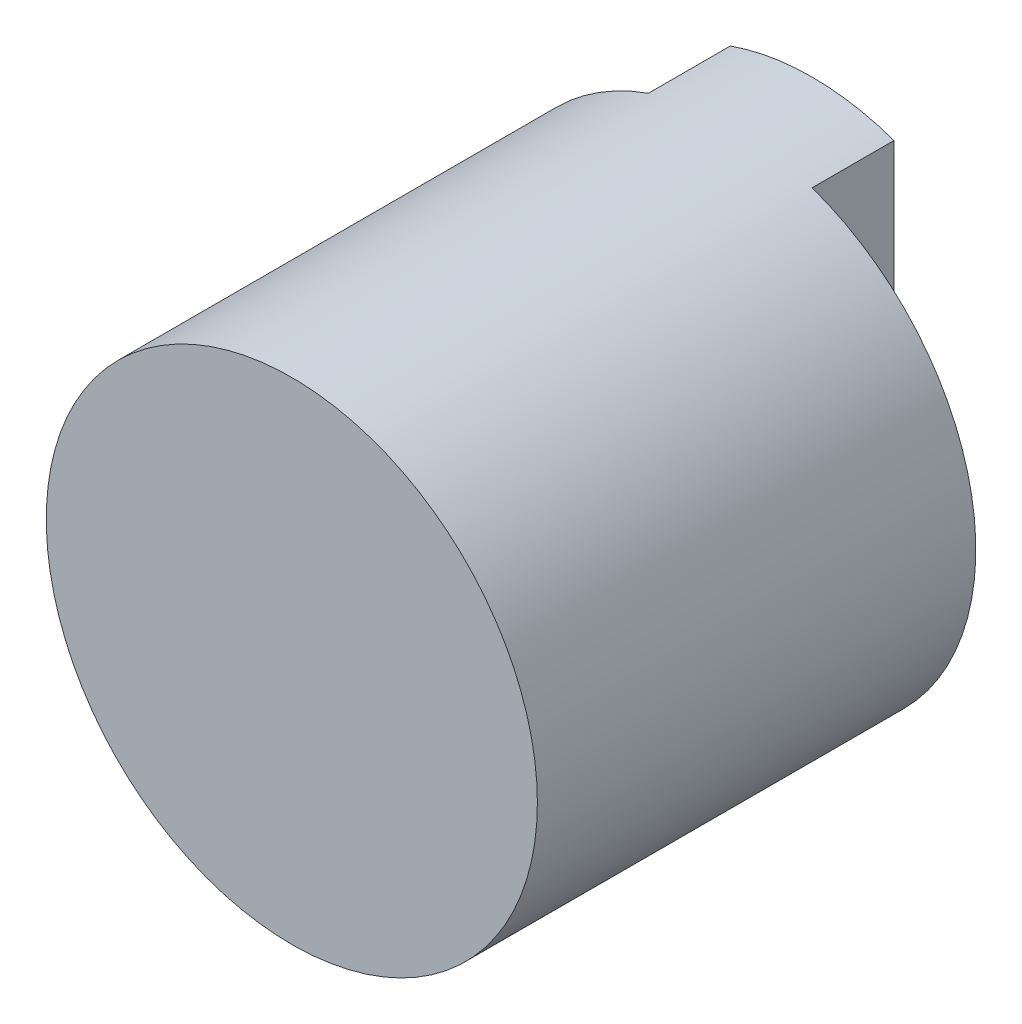
SolidWorks part; units mm, degrees
material "1060 Alloy"
ref_plane "Front Plane" through (0, 0, 0) normal (0, 0, 1) x (1, 0, 0)
ref_plane "Top Plane" through (0, 0, 0) normal (0, 1, 0) x (1, 0, 0)
ref_plane "Right Plane" through (0, 0, 0) normal (1, 0, 0) x (0, 0, -1)
sketch "Sketch1" plane through (0, 0, 0) normal (0, 0, 1) x (1, 0, 0)
  circle A0 centre (0, 0) radius 4.7625
  dimension "D1" = 9.525
extrude "Boss-Extrude1" add sketch "Sketch1" along normal blind 10.0901
sketch "Sketch2" plane through (0, 0, 0) normal (0, 1, 0) x (1, 0, 0)
  line L0 (4.7625, 0) -> (-4.7625, 0) construction
  line L1 (-4.7625, 1.5875) -> (-1.5875, 1.5875)
  line L2 (-4.7625, 1.5875) -> (-4.7625, -1.5875)
  line L3 (-4.7625, -1.5875) -> (-1.5875, -1.5875)
  line L4 (-1.5875, 1.5875) -> (-1.5875, -1.5875)
  line L5 (6.2298, 0.4747) -> (5.8946, 0.4747)
  line L6 (6.2298, 0.4747) -> (6.2298, 0.335)
  line L7 (6.2298, 0.335) -> (5.8946, 0.335)
  line L8 (5.8946, 0.4747) -> (5.8946, 0.335)
  line L9 (4.7625, 1.5875) -> (1.5875, 1.5875)
  line L10 (4.7625, 1.5875) -> (4.7625, -1.5875)
  line L11 (4.7625, -1.5875) -> (1.5875, -1.5875)
  line L12 (1.5875, 1.5875) -> (1.5875, -1.5875)
  dimension "D1" = 9.525
  dimension "D2" = 4.7625
  dimension "D3" = 3.175
  dimension "D4" = 3.175
  dimension "D5" = 3.175
  dimension "D6" = 3.175
  dimension "D7" = 1.5875
  dimension "D8" = 1.5875
extrude "Cut-Extrude1" cut sketch "Sketch2" against normal blind 13.4937 and the other way blind 13.4937
hole_wizard "#4-40 Tapped Hole1" positions "Sketch5" profile "Sketch4" tap size "#4-40" standard "Ansi Inch"
sketch "Sketch5" plane through (0, 0, 0) normal (0, 0, -1) x (-1, 0, 0)
  line L0 (-1.5875, -4.4901) -> (-1.5875, 4.4901) construction
  arc A0 (1.5875, 4.4901) -> (-1.5875, 4.4901) centre (0, 0) ccw construction
  point P0 (0, 0)
  dimension "D1" = 1.5875
  dimension "D2" = 0
sketch "Sketch4" plane through (0, 0, 0) normal (1, 0, 0) x (0, 1, 0)
  line L0 (0, 0) -> (0, 9.5438)
  line L1 (0, 9.5438) -> (1.1303, 8.8646)
  line L2 (1.1303, 8.8646) -> (1.1303, 0)
  line L5 (1.1303, 0) -> (0, 0)
  line L10 (0, 9.5438) -> (-1.1303, 8.8646) construction
  line L11 (0, -6.35) -> (0, 107.95) construction
  dimension "Tap Drill Dia." = 2.2606
  dimension "Tap Drill Depth" = 8.8646
  dimension "Drill Angle" = 118
